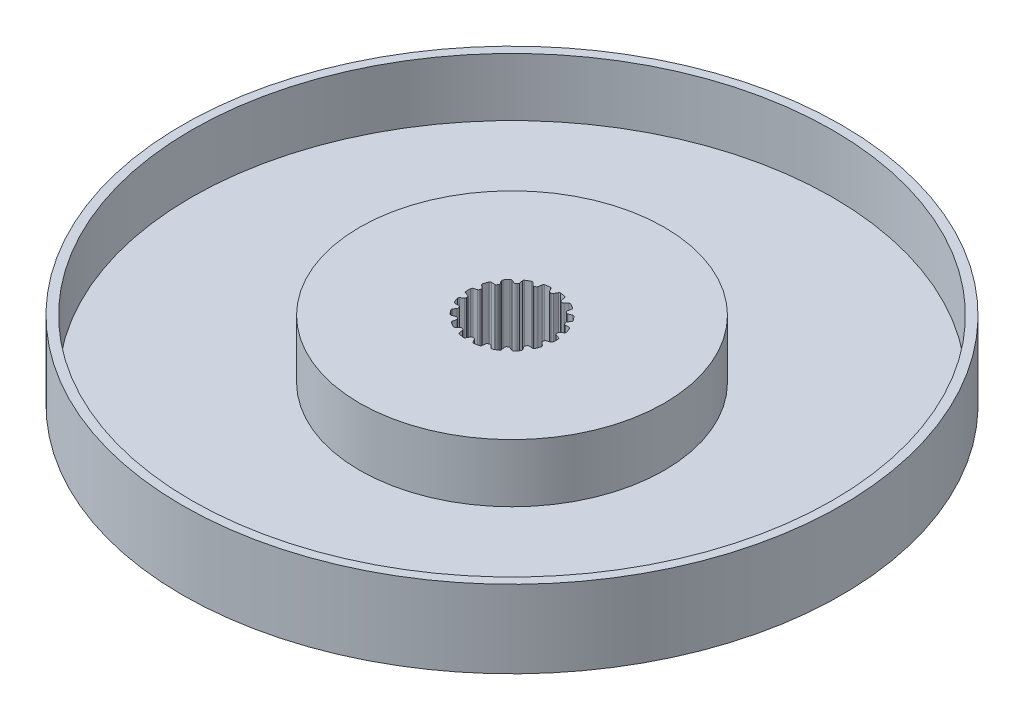
SolidWorks part; units mm, degrees
ref_plane "Front Plane" through (0, 0, 0) normal (0, 0, 1) x (1, 0, 0)
ref_plane "Top Plane" through (0, 0, 0) normal (0, 1, 0) x (1, 0, 0)
ref_plane "Right Plane" through (0, 0, 0) normal (1, 0, 0) x (0, 0, -1)
sketch "Sketch1" plane through (0, 0, 0) normal (0, 1, 0) x (1, 0, 0)
  circle A0 centre (0, 0) radius 42.5
  dimension "D1" = 85
extrude "Boss-Extrude1" add sketch "Sketch1" along normal blind 10
sketch "Sketch2" plane through (0, 10, 10) normal (0, 1, 0) x (1, 0, 0)
  line L1 (-5.2151, 8.5153) -> (-4.9419, 8.7287)
  line L3 (-5.0787, 9.5044) -> (-5.4084, 9.6115)
  line L5 (-5.4084, 10.3885) -> (-5.0787, 10.4956)
  line L7 (-4.9419, 11.2713) -> (-5.2151, 11.4847)
  line L9 (-4.9493, 12.2148) -> (-4.6029, 12.2027)
  line L11 (-4.2091, 12.8848) -> (-4.3928, 13.1788)
  line L13 (-3.8933, 13.774) -> (-3.5719, 13.6442)
  line L15 (-2.9686, 14.1504) -> (-3.0406, 14.4895)
  line L17 (-2.3677, 14.878) -> (-2.1101, 14.6461)
  line L19 (-1.37, 14.9154) -> (-1.3217, 15.2587)
  line L21 (-0.5566, 15.3937) -> (-0.3938, 15.0876)
  line L23 (0.3938, 15.0876) -> (0.5566, 15.3937)
  line L25 (1.3217, 15.2587) -> (1.37, 14.9154)
  line L27 (2.1101, 14.6461) -> (2.3677, 14.878)
  line L29 (3.0406, 14.4895) -> (2.9686, 14.1504)
  line L31 (3.5719, 13.6442) -> (3.8933, 13.774)
  line L33 (4.3928, 13.1788) -> (4.2091, 12.8848)
  line L35 (4.6029, 12.2027) -> (4.9493, 12.2148)
  line L37 (5.2151, 11.4847) -> (4.9419, 11.2713)
  line L39 (5.0787, 10.4956) -> (5.4084, 10.3885)
  line L41 (5.4084, 9.6115) -> (5.0787, 9.5044)
  line L43 (4.9419, 8.7287) -> (5.2151, 8.5153)
  line L45 (4.9493, 7.7852) -> (4.6029, 7.7973)
  line L47 (4.2091, 7.1152) -> (4.3928, 6.8212)
  line L49 (3.8933, 6.226) -> (3.5719, 6.3558)
  line L51 (2.9686, 5.8496) -> (3.0406, 5.5105)
  line L53 (2.3677, 5.122) -> (2.1101, 5.3539)
  line L55 (1.37, 5.0846) -> (1.3217, 4.7413)
  line L57 (0.5566, 4.6063) -> (0.3938, 4.9124)
  line L59 (-0.3938, 4.9124) -> (-0.5566, 4.6063)
  line L61 (-1.3217, 4.7413) -> (-1.37, 5.0846)
  line L63 (-2.1101, 5.3539) -> (-2.3677, 5.122)
  line L65 (-3.0406, 5.5105) -> (-2.9686, 5.8496)
  line L67 (-3.5719, 6.3558) -> (-3.8933, 6.226)
  line L69 (-4.3928, 6.8212) -> (-4.2091, 7.1152)
  line L71 (-4.6029, 7.7973) -> (-4.9493, 7.7852)
  circle A0 centre (0, 10) radius 42.5 construction
  arc A1 (-5.292, 8.2623) -> (-5.1709, 7.9295) centre (0, 10) ccw
  arc A3 (-5.2151, 8.5153) -> (-5.292, 8.2623) centre (-5.0735, 8.334) ccw
  arc A5 (-4.9419, 8.7287) -> (-4.8325, 9.0245) centre (-5.1266, 8.9651) ccw
  arc A7 (-4.8747, 9.2639) -> (-4.8325, 9.0245) centre (0, 10) ccw
  arc A9 (-4.8747, 9.2639) -> (-5.0787, 9.5044) centre (-5.1714, 9.2191) ccw
  arc A11 (-5.5672, 9.8229) -> (-5.4084, 9.6115) centre (-5.3373, 9.8302) ccw
  arc A13 (-5.5672, 10.1771) -> (-5.5672, 9.8229) centre (0, 10) ccw
  arc A15 (-5.4084, 10.3885) -> (-5.5672, 10.1771) centre (-5.3373, 10.1698) ccw
  arc A17 (-5.0787, 10.4956) -> (-4.8747, 10.7361) centre (-5.1714, 10.7809) ccw
  arc A19 (-4.8325, 10.9755) -> (-4.8747, 10.7361) centre (0, 10) ccw
  arc A21 (-4.8325, 10.9755) -> (-4.9419, 11.2713) centre (-5.1266, 11.0349) ccw
  arc A23 (-5.292, 11.7377) -> (-5.2151, 11.4847) centre (-5.0735, 11.666) ccw
  arc A25 (-5.1709, 12.0705) -> (-5.292, 11.7377) centre (0, 10) ccw
  arc A27 (-4.9493, 12.2148) -> (-5.1709, 12.0705) centre (-4.9574, 11.985) ccw
  arc A29 (-4.6029, 12.2027) -> (-4.329, 12.359) centre (-4.5924, 12.5026) ccw
  arc A31 (-4.2074, 12.5695) -> (-4.329, 12.359) centre (0, 10) ccw
  arc A33 (-4.2074, 12.5695) -> (-4.2091, 12.8848) centre (-4.4635, 12.7259) ccw
  arc A35 (-4.3785, 13.4429) -> (-4.3928, 13.1788) centre (-4.1977, 13.3007) ccw
  arc A37 (-4.1509, 13.7142) -> (-4.3785, 13.4429) centre (0, 10) ccw
  arc A39 (-3.8933, 13.774) -> (-4.1509, 13.7142) centre (-3.9795, 13.5608) ccw
  arc A41 (-3.5719, 13.6442) -> (-3.2611, 13.6973) centre (-3.4595, 13.9223) ccw
  arc A43 (-3.0749, 13.8536) -> (-3.2611, 13.6973) centre (0, 10) ccw
  arc A45 (-3.0749, 13.8536) -> (-2.9686, 14.1504) centre (-3.262, 14.0881) ccw
  arc A47 (-2.9369, 14.7328) -> (-3.0406, 14.4895) centre (-2.8157, 14.5374) ccw
  arc A49 (-2.6303, 14.9099) -> (-2.9369, 14.7328) centre (0, 10) ccw
  arc A51 (-2.3677, 14.878) -> (-2.6303, 14.9099) centre (-2.5216, 14.7071) ccw
  arc A53 (-2.1101, 14.6461) -> (-1.7998, 14.5897) centre (-1.9094, 14.869) ccw
  arc A55 (-1.5714, 14.6728) -> (-1.7998, 14.5897) centre (0, 10) ccw
  arc A57 (-1.5714, 14.6728) -> (-1.37, 14.9154) centre (-1.6671, 14.9572) ccw
  arc A59 (-1.1411, 15.4519) -> (-1.3217, 15.2587) centre (-1.094, 15.2267) ccw
  arc A61 (-0.7924, 15.5134) -> (-1.1411, 15.4519) centre (0, 10) ccw
  arc A63 (-0.5566, 15.3937) -> (-0.7924, 15.5134) centre (-0.7596, 15.2857) ccw
  arc A65 (-0.3938, 15.0876) -> (-0.1215, 14.9285) centre (-0.1289, 15.2284) ccw
  arc A67 (0.1215, 14.9285) -> (-0.1215, 14.9285) centre (0, 10) ccw
  arc A69 (0.1215, 14.9285) -> (0.3938, 15.0876) centre (0.1289, 15.2284) ccw
  arc A71 (0.7924, 15.5134) -> (0.5566, 15.3937) centre (0.7596, 15.2857) ccw
  arc A73 (1.1411, 15.4519) -> (0.7924, 15.5134) centre (0, 10) ccw
  arc A75 (1.3217, 15.2587) -> (1.1411, 15.4519) centre (1.094, 15.2267) ccw
  arc A77 (1.37, 14.9154) -> (1.5714, 14.6728) centre (1.6671, 14.9572) ccw
  arc A79 (1.7998, 14.5897) -> (1.5714, 14.6728) centre (0, 10) ccw
  arc A81 (1.7998, 14.5897) -> (2.1101, 14.6461) centre (1.9094, 14.869) ccw
  arc A83 (2.6303, 14.9099) -> (2.3677, 14.878) centre (2.5216, 14.7071) ccw
  arc A85 (2.9369, 14.7328) -> (2.6303, 14.9099) centre (0, 10) ccw
  arc A87 (3.0406, 14.4895) -> (2.9369, 14.7328) centre (2.8157, 14.5374) ccw
  arc A89 (2.9686, 14.1504) -> (3.0749, 13.8536) centre (3.262, 14.0881) ccw
  arc A91 (3.2611, 13.6973) -> (3.0749, 13.8536) centre (0, 10) ccw
  arc A93 (3.2611, 13.6973) -> (3.5719, 13.6442) centre (3.4595, 13.9223) ccw
  arc A95 (4.1509, 13.7142) -> (3.8933, 13.774) centre (3.9795, 13.5608) ccw
  arc A97 (4.3785, 13.4429) -> (4.1509, 13.7142) centre (0, 10) ccw
  arc A99 (4.3928, 13.1788) -> (4.3785, 13.4429) centre (4.1977, 13.3007) ccw
  arc A101 (4.2091, 12.8848) -> (4.2074, 12.5695) centre (4.4635, 12.7259) ccw
  arc A103 (4.329, 12.359) -> (4.2074, 12.5695) centre (0, 10) ccw
  arc A105 (4.329, 12.359) -> (4.6029, 12.2027) centre (4.5924, 12.5026) ccw
  arc A107 (5.1709, 12.0705) -> (4.9493, 12.2148) centre (4.9574, 11.985) ccw
  arc A109 (5.292, 11.7377) -> (5.1709, 12.0705) centre (0, 10) ccw
  arc A111 (5.2151, 11.4847) -> (5.292, 11.7377) centre (5.0735, 11.666) ccw
  arc A113 (4.9419, 11.2713) -> (4.8325, 10.9755) centre (5.1266, 11.0349) ccw
  arc A115 (4.8747, 10.7361) -> (4.8325, 10.9755) centre (0, 10) ccw
  arc A117 (4.8747, 10.7361) -> (5.0787, 10.4956) centre (5.1714, 10.7809) ccw
  arc A119 (5.5672, 10.1771) -> (5.4084, 10.3885) centre (5.3373, 10.1698) ccw
  arc A121 (5.5672, 9.8229) -> (5.5672, 10.1771) centre (0, 10) ccw
  arc A123 (5.4084, 9.6115) -> (5.5672, 9.8229) centre (5.3373, 9.8302) ccw
  arc A125 (5.0787, 9.5044) -> (4.8747, 9.2639) centre (5.1714, 9.2191) ccw
  arc A127 (4.8325, 9.0245) -> (4.8747, 9.2639) centre (0, 10) ccw
  arc A129 (4.8325, 9.0245) -> (4.9419, 8.7287) centre (5.1266, 8.9651) ccw
  arc A131 (5.292, 8.2623) -> (5.2151, 8.5153) centre (5.0735, 8.334) ccw
  arc A133 (5.1709, 7.9295) -> (5.292, 8.2623) centre (0, 10) ccw
  arc A135 (4.9493, 7.7852) -> (5.1709, 7.9295) centre (4.9574, 8.015) ccw
  arc A137 (4.6029, 7.7973) -> (4.329, 7.641) centre (4.5924, 7.4974) ccw
  arc A139 (4.2074, 7.4305) -> (4.329, 7.641) centre (0, 10) ccw
  arc A141 (4.2074, 7.4305) -> (4.2091, 7.1152) centre (4.4635, 7.2741) ccw
  arc A143 (4.3785, 6.5571) -> (4.3928, 6.8212) centre (4.1977, 6.6993) ccw
  arc A145 (4.1509, 6.2858) -> (4.3785, 6.5571) centre (0, 10) ccw
  arc A147 (3.8933, 6.226) -> (4.1509, 6.2858) centre (3.9795, 6.4392) ccw
  arc A149 (3.5719, 6.3558) -> (3.2611, 6.3027) centre (3.4595, 6.0777) ccw
  arc A151 (3.0749, 6.1464) -> (3.2611, 6.3027) centre (0, 10) ccw
  arc A153 (3.0749, 6.1464) -> (2.9686, 5.8496) centre (3.262, 5.9119) ccw
  arc A155 (2.9369, 5.2672) -> (3.0406, 5.5105) centre (2.8157, 5.4626) ccw
  arc A157 (2.6303, 5.0901) -> (2.9369, 5.2672) centre (0, 10) ccw
  arc A159 (2.3677, 5.122) -> (2.6303, 5.0901) centre (2.5216, 5.2929) ccw
  arc A161 (2.1101, 5.3539) -> (1.7998, 5.4103) centre (1.9094, 5.131) ccw
  arc A163 (1.5714, 5.3272) -> (1.7998, 5.4103) centre (0, 10) ccw
  arc A165 (1.5714, 5.3272) -> (1.37, 5.0846) centre (1.6671, 5.0428) ccw
  arc A167 (1.1411, 4.5481) -> (1.3217, 4.7413) centre (1.094, 4.7733) ccw
  arc A169 (0.7924, 4.4866) -> (1.1411, 4.5481) centre (0, 10) ccw
  arc A171 (0.5566, 4.6063) -> (0.7924, 4.4866) centre (0.7596, 4.7143) ccw
  arc A173 (0.3938, 4.9124) -> (0.1215, 5.0715) centre (0.1289, 4.7716) ccw
  arc A175 (-0.1215, 5.0715) -> (0.1215, 5.0715) centre (0, 10) ccw
  arc A177 (-0.1215, 5.0715) -> (-0.3938, 4.9124) centre (-0.1289, 4.7716) ccw
  arc A179 (-0.7924, 4.4866) -> (-0.5566, 4.6063) centre (-0.7596, 4.7143) ccw
  arc A181 (-1.1411, 4.5481) -> (-0.7924, 4.4866) centre (0, 10) ccw
  arc A183 (-1.3217, 4.7413) -> (-1.1411, 4.5481) centre (-1.094, 4.7733) ccw
  arc A185 (-1.37, 5.0846) -> (-1.5714, 5.3272) centre (-1.6671, 5.0428) ccw
  arc A187 (-1.7998, 5.4103) -> (-1.5714, 5.3272) centre (0, 10) ccw
  arc A189 (-1.7998, 5.4103) -> (-2.1101, 5.3539) centre (-1.9094, 5.131) ccw
  arc A191 (-2.6303, 5.0901) -> (-2.3677, 5.122) centre (-2.5216, 5.2929) ccw
  arc A193 (-2.9369, 5.2672) -> (-2.6303, 5.0901) centre (0, 10) ccw
  arc A195 (-3.0406, 5.5105) -> (-2.9369, 5.2672) centre (-2.8157, 5.4626) ccw
  arc A197 (-2.9686, 5.8496) -> (-3.0749, 6.1464) centre (-3.262, 5.9119) ccw
  arc A199 (-3.2611, 6.3027) -> (-3.0749, 6.1464) centre (0, 10) ccw
  arc A201 (-3.2611, 6.3027) -> (-3.5719, 6.3558) centre (-3.4595, 6.0777) ccw
  arc A203 (-4.1509, 6.2858) -> (-3.8933, 6.226) centre (-3.9795, 6.4392) ccw
  arc A205 (-4.3785, 6.5571) -> (-4.1509, 6.2858) centre (0, 10) ccw
  arc A207 (-4.3928, 6.8212) -> (-4.3785, 6.5571) centre (-4.1977, 6.6993) ccw
  arc A209 (-4.2091, 7.1152) -> (-4.2074, 7.4305) centre (-4.4635, 7.2741) ccw
  arc A211 (-4.329, 7.641) -> (-4.2074, 7.4305) centre (0, 10) ccw
  arc A213 (-4.329, 7.641) -> (-4.6029, 7.7973) centre (-4.5924, 7.4974) ccw
  arc A215 (-5.1709, 7.9295) -> (-4.9493, 7.7852) centre (-4.9574, 8.015) ccw
  dimension "D1" = 0
extrude "Cut-Extrude1" [suppressed] cut sketch "Sketch2" against normal blind 10
sketch "Sketch3" plane through (0, 10, 0) normal (0, 1, 0) x (1, 0, 0)
  circle A0 centre (0, 0) radius 19.65
  circle A1 centre (0, 0) radius 41.35
  dimension "D1" = 82.7
  dimension "D2" = 39.3
extrude "Cut-Extrude2" cut sketch "Sketch3" against normal blind 7.5
sketch "Sketch4" plane through (0, 10, 0) normal (0, 1, 0) x (1, 0, 0)
  line L0 (0, 0) -> (0, 6) construction
  line L1 (-0.4643, 5.5061) -> (-0.2516, 5.1061)
  line L2 (-0.075, 5) -> (0.075, 5)
  line L3 (0.2516, 5.1061) -> (0.4643, 5.5061)
  line L4 (0, 0) -> (-0.6644, 5.6108) construction
  line L5 (0, 0) -> (1.2947, 5.4997) construction
  line L6 (1.4469, 5.3328) -> (1.51, 4.8842)
  line L7 (1.6396, 4.7241) -> (1.7806, 4.6728)
  line L8 (1.9828, 4.7121) -> (2.3195, 5.0152)
  line L9 (3.1836, 4.5163) -> (3.0894, 4.0732)
  line L10 (3.1565, 3.8784) -> (3.2714, 3.782)
  line L11 (3.4749, 3.7498) -> (3.8949, 3.9195)
  line L12 (4.5363, 3.1551) -> (4.2962, 2.7709)
  line L13 (4.2926, 2.565) -> (4.3676, 2.435)
  line L14 (4.5478, 2.3352) -> (5.0005, 2.351)
  line L15 (5.3418, 1.4133) -> (4.9848, 1.1344)
  line L16 (4.911, 0.9421) -> (4.9371, 0.7944)
  line L17 (5.0722, 0.6389) -> (5.5031, 0.4989)
  line L18 (5.5031, -0.4989) -> (5.0722, -0.6389)
  line L19 (4.9371, -0.7944) -> (4.911, -0.9421)
  line L20 (4.9848, -1.1344) -> (5.3418, -1.4133)
  line L21 (5.0005, -2.351) -> (4.5478, -2.3352)
  line L22 (4.3676, -2.435) -> (4.2926, -2.565)
  line L23 (4.2962, -2.7709) -> (4.5363, -3.1551)
  line L24 (3.8949, -3.9195) -> (3.4749, -3.7498)
  line L25 (3.2714, -3.782) -> (3.1565, -3.8784)
  line L26 (3.0894, -4.0732) -> (3.1836, -4.5163)
  line L27 (2.3195, -5.0152) -> (1.9828, -4.7121)
  line L28 (1.7806, -4.6728) -> (1.6396, -4.7241)
  line L29 (1.51, -4.8842) -> (1.4469, -5.3328)
  line L30 (0.4643, -5.5061) -> (0.2516, -5.1061)
  line L31 (0.075, -5) -> (-0.075, -5)
  line L32 (-0.2516, -5.1061) -> (-0.4643, -5.5061)
  line L33 (-1.4469, -5.3328) -> (-1.51, -4.8842)
  line L34 (-1.6396, -4.7241) -> (-1.7806, -4.6728)
  line L35 (-1.9828, -4.7121) -> (-2.3195, -5.0152)
  line L36 (-3.1836, -4.5163) -> (-3.0894, -4.0732)
  line L37 (-3.1565, -3.8784) -> (-3.2714, -3.782)
  line L38 (-3.4749, -3.7498) -> (-3.8949, -3.9195)
  line L39 (-4.5363, -3.1551) -> (-4.2962, -2.7709)
  line L40 (-4.2926, -2.565) -> (-4.3676, -2.435)
  line L41 (-4.5478, -2.3352) -> (-5.0005, -2.351)
  line L42 (-5.3418, -1.4133) -> (-4.9848, -1.1344)
  line L43 (-4.911, -0.9421) -> (-4.9371, -0.7944)
  line L44 (-5.0722, -0.6389) -> (-5.5031, -0.4989)
  line L45 (-5.5031, 0.4989) -> (-5.0722, 0.6389)
  line L46 (-4.9371, 0.7944) -> (-4.911, 0.9421)
  line L47 (-4.9848, 1.1344) -> (-5.3418, 1.4133)
  line L48 (-5.0005, 2.351) -> (-4.5478, 2.3352)
  line L49 (-4.3676, 2.435) -> (-4.2926, 2.565)
  line L50 (-4.2962, 2.7709) -> (-4.5363, 3.1551)
  line L51 (-3.8949, 3.9195) -> (-3.4749, 3.7498)
  line L52 (-3.2714, 3.782) -> (-3.1565, 3.8784)
  line L53 (-3.0894, 4.0732) -> (-3.1836, 4.5163)
  line L54 (-2.3195, 5.0152) -> (-1.9828, 4.7121)
  line L55 (-1.7806, 4.6728) -> (-1.6396, 4.7241)
  line L56 (-1.51, 4.8842) -> (-1.4469, 5.3328)
  arc A1 (0.075, 5) -> (0.2516, 5.1061) centre (0.075, 5.2) ccw
  arc A2 (-0.2516, 5.1061) -> (-0.075, 5) centre (-0.075, 5.2) ccw
  arc A5 (-0.6644, 5.6108) -> (0.6644, 5.6108) centre (0, 0) ccw construction
  arc A6 (0.4643, 5.5061) -> (0.6644, 5.6108) centre (0.6409, 5.4122) cw
  arc A7 (-0.4643, 5.5061) -> (-0.6644, 5.6108) centre (-0.6409, 5.4122) ccw
  arc A8 (1.7806, 4.6728) -> (1.9828, 4.7121) centre (1.849, 4.8608) ccw
  arc A9 (1.51, 4.8842) -> (1.6396, 4.7241) centre (1.708, 4.9121) ccw
  arc A10 (2.3195, 5.0152) -> (2.5433, 5.0452) centre (2.4533, 4.8666) cw
  arc A11 (1.4469, 5.3328) -> (1.2947, 5.4997) centre (1.2489, 5.305) ccw
  arc A12 (3.2714, 3.782) -> (3.4749, 3.7498) centre (3.3999, 3.9352) ccw
  arc A13 (3.0894, 4.0732) -> (3.1565, 3.8784) centre (3.285, 4.0316) ccw
  arc A14 (3.8949, 3.9195) -> (4.1155, 3.8711) centre (3.9698, 3.734) cw
  arc A15 (3.1836, 4.5163) -> (3.0976, 4.7252) centre (2.988, 4.5579) ccw
  arc A16 (4.3676, 2.435) -> (4.5478, 2.3352) centre (4.5408, 2.535) ccw
  arc A17 (4.2962, 2.7709) -> (4.2926, 2.565) centre (4.4658, 2.665) ccw
  arc A18 (5.0005, 2.351) -> (5.1913, 2.23) centre (5.0075, 2.1511) cw
  arc A19 (4.5363, 3.1551) -> (4.5269, 3.3808) centre (4.3667, 3.2611) ccw
  arc A20 (4.9371, 0.7944) -> (5.0722, 0.6389) centre (5.134, 0.8291) ccw
  arc A21 (4.9848, 1.1344) -> (4.911, 0.9421) centre (5.108, 0.9768) ccw
  arc A22 (5.5031, 0.4989) -> (5.6409, 0.32) centre (5.4413, 0.3087) cw
  arc A23 (5.3418, 1.4133) -> (5.4102, 1.6286) centre (5.2187, 1.5709) ccw
  arc A24 (4.911, -0.9421) -> (4.9848, -1.1344) centre (5.108, -0.9768) ccw
  arc A25 (5.0722, -0.6389) -> (4.9371, -0.7944) centre (5.134, -0.8291) ccw
  arc A26 (5.3418, -1.4133) -> (5.4102, -1.6286) centre (5.2187, -1.5709) cw
  arc A27 (5.5031, -0.4989) -> (5.6409, -0.32) centre (5.4413, -0.3087) ccw
  arc A28 (4.2926, -2.565) -> (4.2962, -2.7709) centre (4.4658, -2.665) ccw
  arc A29 (4.5478, -2.3352) -> (4.3676, -2.435) centre (4.5408, -2.535) ccw
  arc A30 (4.5363, -3.1551) -> (4.5269, -3.3808) centre (4.3667, -3.2611) cw
  arc A31 (5.0005, -2.351) -> (5.1913, -2.23) centre (5.0075, -2.1511) ccw
  arc A32 (3.1565, -3.8784) -> (3.0894, -4.0732) centre (3.285, -4.0316) ccw
  arc A33 (3.4749, -3.7498) -> (3.2714, -3.782) centre (3.3999, -3.9352) ccw
  arc A34 (3.1836, -4.5163) -> (3.0976, -4.7252) centre (2.988, -4.5579) cw
  arc A35 (3.8949, -3.9195) -> (4.1155, -3.8711) centre (3.9698, -3.734) ccw
  arc A36 (1.6396, -4.7241) -> (1.51, -4.8842) centre (1.708, -4.9121) ccw
  arc A37 (1.9828, -4.7121) -> (1.7806, -4.6728) centre (1.849, -4.8608) ccw
  arc A38 (1.4469, -5.3328) -> (1.2947, -5.4997) centre (1.2489, -5.305) cw
  arc A39 (2.3195, -5.0152) -> (2.5433, -5.0452) centre (2.4533, -4.8666) ccw
  arc A40 (-0.075, -5) -> (-0.2516, -5.1061) centre (-0.075, -5.2) ccw
  arc A41 (0.2516, -5.1061) -> (0.075, -5) centre (0.075, -5.2) ccw
  arc A42 (-0.4643, -5.5061) -> (-0.6644, -5.6108) centre (-0.6409, -5.4122) cw
  arc A43 (0.4643, -5.5061) -> (0.6644, -5.6108) centre (0.6409, -5.4122) ccw
  arc A44 (-1.7806, -4.6728) -> (-1.9828, -4.7121) centre (-1.849, -4.8608) ccw
  arc A45 (-1.51, -4.8842) -> (-1.6396, -4.7241) centre (-1.708, -4.9121) ccw
  arc A46 (-2.3195, -5.0152) -> (-2.5433, -5.0452) centre (-2.4533, -4.8666) cw
  arc A47 (-1.4469, -5.3328) -> (-1.2947, -5.4997) centre (-1.2489, -5.305) ccw
  arc A48 (-3.2714, -3.782) -> (-3.4749, -3.7498) centre (-3.3999, -3.9352) ccw
  arc A49 (-3.0894, -4.0732) -> (-3.1565, -3.8784) centre (-3.285, -4.0316) ccw
  arc A50 (-3.8949, -3.9195) -> (-4.1155, -3.8711) centre (-3.9698, -3.734) cw
  arc A51 (-3.1836, -4.5163) -> (-3.0976, -4.7252) centre (-2.988, -4.5579) ccw
  arc A52 (-4.3676, -2.435) -> (-4.5478, -2.3352) centre (-4.5408, -2.535) ccw
  arc A53 (-4.2962, -2.7709) -> (-4.2926, -2.565) centre (-4.4658, -2.665) ccw
  arc A54 (-5.0005, -2.351) -> (-5.1913, -2.23) centre (-5.0075, -2.1511) cw
  arc A55 (-4.5363, -3.1551) -> (-4.5269, -3.3808) centre (-4.3667, -3.2611) ccw
  arc A56 (-4.9371, -0.7944) -> (-5.0722, -0.6389) centre (-5.134, -0.8291) ccw
  arc A57 (-4.9848, -1.1344) -> (-4.911, -0.9421) centre (-5.108, -0.9768) ccw
  arc A58 (-5.5031, -0.4989) -> (-5.6409, -0.32) centre (-5.4413, -0.3087) cw
  arc A59 (-5.3418, -1.4133) -> (-5.4102, -1.6286) centre (-5.2187, -1.5709) ccw
  arc A60 (-4.911, 0.9421) -> (-4.9848, 1.1344) centre (-5.108, 0.9768) ccw
  arc A61 (-5.0722, 0.6389) -> (-4.9371, 0.7944) centre (-5.134, 0.8291) ccw
  arc A62 (-5.3418, 1.4133) -> (-5.4102, 1.6286) centre (-5.2187, 1.5709) cw
  arc A63 (-5.5031, 0.4989) -> (-5.6409, 0.32) centre (-5.4413, 0.3087) ccw
  arc A64 (-4.2926, 2.565) -> (-4.2962, 2.7709) centre (-4.4658, 2.665) ccw
  arc A65 (-4.5478, 2.3352) -> (-4.3676, 2.435) centre (-4.5408, 2.535) ccw
  arc A66 (-4.5363, 3.1551) -> (-4.5269, 3.3808) centre (-4.3667, 3.2611) cw
  arc A67 (-5.0005, 2.351) -> (-5.1913, 2.23) centre (-5.0075, 2.1511) ccw
  arc A68 (-3.1565, 3.8784) -> (-3.0894, 4.0732) centre (-3.285, 4.0316) ccw
  arc A69 (-3.4749, 3.7498) -> (-3.2714, 3.782) centre (-3.3999, 3.9352) ccw
  arc A70 (-3.1836, 4.5163) -> (-3.0976, 4.7252) centre (-2.988, 4.5579) cw
  arc A71 (-3.8949, 3.9195) -> (-4.1155, 3.8711) centre (-3.9698, 3.734) ccw
  arc A72 (-1.6396, 4.7241) -> (-1.51, 4.8842) centre (-1.708, 4.9121) ccw
  arc A73 (-1.9828, 4.7121) -> (-1.7806, 4.6728) centre (-1.849, 4.8608) ccw
  arc A74 (-1.4469, 5.3328) -> (-1.2947, 5.4997) centre (-1.2489, 5.305) cw
  arc A75 (-2.3195, 5.0152) -> (-2.5433, 5.0452) centre (-2.4533, 4.8666) ccw
  arc A76 (0.6644, 5.6108) -> (1.2947, 5.4997) centre (0, 0) cw
  arc A77 (2.5433, 5.0452) -> (3.0976, 4.7252) centre (0, 0) cw
  arc A78 (4.1155, 3.8711) -> (4.5269, 3.3808) centre (0, 0) cw
  arc A79 (5.1913, 2.23) -> (5.4102, 1.6286) centre (0, 0) cw
  arc A80 (5.6409, 0.32) -> (5.6409, -0.32) centre (0, 0) cw
  arc A81 (5.4102, -1.6286) -> (5.1913, -2.23) centre (0, 0) cw
  arc A82 (4.5269, -3.3808) -> (4.1155, -3.8711) centre (0, 0) cw
  arc A83 (3.0976, -4.7252) -> (2.5433, -5.0452) centre (0, 0) cw
  arc A84 (1.2947, -5.4997) -> (0.6644, -5.6108) centre (0, 0) cw
  arc A85 (-0.6644, -5.6108) -> (-1.2947, -5.4997) centre (0, 0) cw
  arc A86 (-2.5433, -5.0452) -> (-3.0976, -4.7252) centre (0, 0) cw
  arc A87 (-4.1155, -3.8711) -> (-4.5269, -3.3808) centre (0, 0) cw
  arc A88 (-5.1913, -2.23) -> (-5.4102, -1.6286) centre (0, 0) cw
  arc A89 (-5.6409, -0.32) -> (-5.6409, 0.32) centre (0, 0) cw
  arc A90 (-5.4102, 1.6286) -> (-5.1913, 2.23) centre (0, 0) cw
  arc A91 (-4.5269, 3.3808) -> (-4.1155, 3.8711) centre (0, 0) cw
  arc A92 (-3.0976, 4.7252) -> (-2.5433, 5.0452) centre (0, 0) cw
  arc A93 (-1.2947, 5.4997) -> (-0.6644, 5.6108) centre (0, 0) cw
  point P14 (0.1952, 5)
  point P17 (-0.1952, 5)
  point P225 (0, 0)
  point P260 (0, 0)
  dimension "D6" = 0.2
  dimension "D7" = 11.3
  dimension "D10" = 0.2
  dimension "D2" = 28
  dimension "D3" = 28
  dimension "D8" = 0.15
  dimension "D9" = 20
  dimension "D4" = 0.075
  dimension "D5" = 5
  dimension "D12" = 18
  dimension "D11" = 18
extrude "Cut-Extrude4" cut sketch "Sketch4" against normal through all contours A93 A74 L56 A72 L55 A73 L54 A75 A92 A70 L53 A68 L52 A69 L51 A71 A91 A66 L50 A64 L49 A65 L48 A67 A90 A62 L47 A60 L46 A61 L45 A63 A89 A58 L44 A56 L43 A57 L42 A59 A88 A54 L41 A52 L40 A53 L39 A55 A87 A50 L38 region at (0, 10, 0)
sketch "Sketch5" plane through (0, 10, 0) normal (0, 1, 0) x (1, 0, 0)
  circle A0 centre (0, 0) radius 7.5
  circle A1 centre (0, 0) radius 50
  dimension "D1" = 100
  dimension "D2" = 15
extrude "Cut-Extrude5" [suppressed] cut sketch "Sketch5" against normal through all
equation "\"D4@Sketch4\"=\"D8@Sketch4\"/2"
